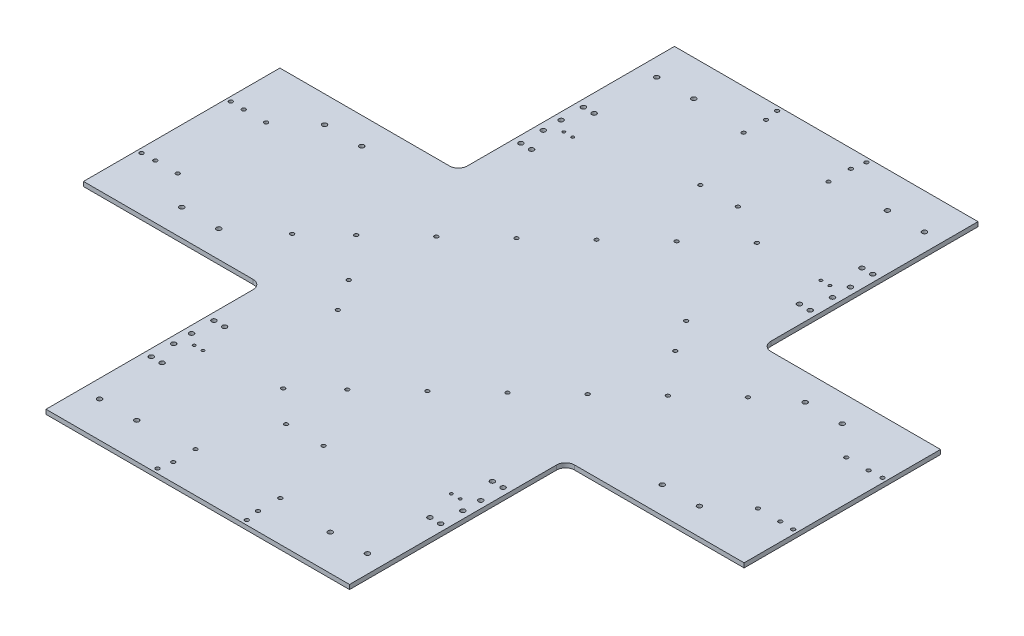
SolidWorks part; units mm, degrees
other "Markup1"
sketch "Sketch8"
material "3.0205 (EN-AW 1200)"
ref_plane "前视基准面" through (0, 0, 0) normal (0, 0, 1) x (1, 0, 0)
ref_plane "上视基准面" through (0, 0, 0) normal (0, 1, 0) x (1, 0, 0)
ref_plane "右视基准面" through (0, 0, 0) normal (1, 0, 0) x (0, 0, -1)
other "Configuration Table"
sketch "Sketch1" plane through (0, 0, 0) normal (0, 1, 0) x (1, 0, 0)
  line L0 (170, 352) -> (-170, 352)
  line L1 (-170, 352) -> (-170, 110)
  line L2 (-170, 110) -> (-370, 110)
  line L5 (-370, 110) -> (-370, -110)
  line L6 (0, 352) -> (0, -66.8675) construction
  line L7 (-370, 0) -> (131.0517, 0) construction
  line L8 (370, 110) -> (370, -110)
  line L11 (170, 110) -> (370, 110)
  line L12 (170, 352) -> (170, 110)
  line L13 (170, -352) -> (170, -110)
  line L14 (170, -110) -> (370, -110)
  line L19 (-170, -110) -> (-370, -110)
  line L20 (-170, -352) -> (-170, -110)
  line L21 (170, -352) -> (-170, -352)
  point P21 (370, 0)
  dimension "D1" = 170
  dimension "D2" = 200
  dimension "D3" = 110
  dimension "D4" = 242
extrude "Boss-Extrude1" add sketch "Sketch1" along normal blind 5
sketch "Sketch2" plane through (0, 5, 0) normal (0, 1, 0) x (1, 0, 0)
  line L3 (370, -110) -> (370, 110) construction
  line L4 (-56.7455, 0) -> (47.5165, 0) construction
  line L5 (0, 54.7142) -> (0, -64.2255) construction
  line L7 (170, 352) -> (-170, 352) construction
  circle A0 centre (350, 49.5) radius 2.125
  circle A1 centre (325, 49.5) radius 2.125
  circle A7 centre (325, -49.5) radius 2.125
  circle A8 centre (350, -49.5) radius 2.125
  circle A9 centre (-350, -49.5) radius 2.125
  circle A10 centre (-325, -49.5) radius 2.125
  circle A13 centre (-325, 49.5) radius 2.125
  circle A14 centre (-350, 49.5) radius 2.125
  circle A15 centre (47.5, 332) radius 2.125
  circle A16 centre (47.5, 307) radius 2.125
  circle A17 centre (-47.5, 307) radius 2.125
  circle A18 centre (-47.5, 332) radius 2.125
  circle A19 centre (-47.5, -332) radius 2.125
  circle A20 centre (-47.5, -307) radius 2.125
  circle A21 centre (47.5, -307) radius 2.125
  circle A22 centre (47.5, -332) radius 2.125
  dimension "D3" = 49.5
  dimension "D5" = 4.25
  dimension "D7" = 4.25
  dimension "D9" = 4.25
  dimension "D10" = 4.25
  dimension "D2" = 47.5
  dimension "D4" = 25
  dimension "D6" = 20
  dimension "20" = 20
  dimension "D13" = 25
extrude "Cut-Extrude1" cut sketch "Sketch2" against normal blind 3
sketch "Sketch4" plane through (0, 5, 0) normal (0, 1, 0) x (1, 0, 0)
  line L0 (-170, 352) -> (-170, 110) construction
  line L1 (170, 352) -> (-170, 352) construction
  line L2 (0, 46.9886) -> (0, -40.2904) construction
  line L3 (-35.103, 0) -> (92.4951, 0) construction
  line L5 (170, -352) -> (170, -110) construction
  circle A0 centre (-162, 172) radius 2.6
  circle A1 centre (-150, 172) radius 2.6
  circle A2 centre (-162, 197) radius 2.6
  circle A3 centre (-162, 217) radius 2.6
  circle A4 centre (-162, 242) radius 2.6
  circle A5 centre (-150, 242) radius 2.6
  circle A6 centre (150, 242) radius 2.6
  circle A7 centre (162, 242) radius 2.6
  circle A8 centre (162, 217) radius 2.6
  circle A9 centre (162, 197) radius 2.6
  circle A10 centre (150, 172) radius 2.6
  circle A11 centre (162, 172) radius 2.6
  circle A12 centre (162, -172) radius 2.6
  circle A13 centre (150, -172) radius 2.6
  circle A14 centre (162, -197) radius 2.6
  circle A15 centre (162, -217) radius 2.6
  circle A16 centre (162, -242) radius 2.6
  circle A17 centre (150, -242) radius 2.6
  circle A18 centre (-150, -242) radius 2.6
  circle A19 centre (-162, -242) radius 2.6
  circle A20 centre (-162, -217) radius 2.6
  circle A21 centre (-162, -197) radius 2.6
  circle A22 centre (-150, -172) radius 2.6
  circle A23 centre (-162, -172) radius 2.6
  circle A24 centre (149, -207) radius 1.6
  circle A25 centre (-149, -207) radius 1.6
  circle A26 centre (149, 207) radius 1.6
  circle A27 centre (-149, 207) radius 1.6
  circle A28 centre (139, -207) radius 1.6
  circle A29 centre (-139, -207) radius 1.6
  circle A30 centre (139, 207) radius 1.6
  circle A31 centre (-139, 207) radius 1.6
  dimension "D3" = 5.2
  dimension "D4" = 5.2
  dimension "D5" = 8
  dimension "D6" = 8
  dimension "D9" = 5.2
  dimension "D10" = 5.2
  dimension "D11" = 5.2
  dimension "D12" = 5.2
  dimension "D19" = 3.2
  dimension "D20" = 21
  dimension "D21" = 10
  dimension "D22" = 3.2
  dimension "D23" = 10
  dimension "D1" = 8
  dimension "D2" = 20
  dimension "D7" = 8
  dimension "D8" = 20
  dimension "D13" = 25
  dimension "D14" = 20
  dimension "D15" = 25
  dimension "D16" = 25
  dimension "D17" = 110
  dimension "D18" = 0
extrude "Cut-Extrude3" cut sketch "Sketch4" against normal blind 10
sketch "Sketch5" plane through (0, 5, 0) normal (0, 1, 0) x (1, 0, 0)
  line L0 (170, 352) -> (-170, 352) construction
  line L5 (-46.9195, 0) -> (66.6223, 0) construction
  line L6 (0, 59.0569) -> (0, -54.4849) construction
  line L10 (-370, 110) -> (-370, -110) construction
  circle A0 centre (-50, 347) radius 2.125
  circle A1 centre (50, 347) radius 2.125
  circle A2 centre (50, -347) radius 2.125
  circle A3 centre (-50, -347) radius 2.125
  circle A4 centre (-365, 50) radius 2.125
  circle A5 centre (-365, -50) radius 2.125
  circle A6 centre (365, -50) radius 2.125
  circle A7 centre (365, 50) radius 2.125
  dimension "D1" = 4.25
  dimension "D2" = 4.25
  dimension "D3" = 50
  dimension "D6" = 4.25
  dimension "D7" = 4.25
  dimension "5" = 5
  dimension "D4" = 50
  dimension "D5" = 50
  dimension "D8" = 50
  dimension "D9" = 5
  dimension "D10" = 5
extrude "Cut-Extrude4" cut sketch "Sketch5" against normal blind 10
fillet "Fillet1" radius 10 4 edges at (-170, 2.5, -110) (-170, 2.5, 110) (170, 2.5, 110) (170, 2.5, -110)
sketch "Sketch6" plane through (0, 5, 0) normal (0, 1, 0) x (1, 0, 0)
  line L0 (170, 352) -> (-170, 352) construction
  line L1 (-170, 352) -> (-170, 120) construction
  line L3 (0, 50.3702) -> (0, -42.7646) construction
  line L4 (-54.8568, 0) -> (91.2004, 0) construction
  line L5 (370, 110) -> (180, 110) construction
  line L6 (370, -110) -> (370, 110) construction
  circle A0 centre (-150, 312) radius 2.6
  circle A1 centre (-108.4, 312) radius 2.6
  circle A4 centre (108.4, 312) radius 2.6
  circle A5 centre (150, 312) radius 2.6
  circle A6 centre (150, -312) radius 2.6
  circle A7 centre (108.4, -312) radius 2.6
  circle A8 centre (-108.4, -312) radius 2.6
  circle A9 centre (-150, -312) radius 2.6
  circle A10 centre (248.4, 80) radius 2.6
  circle A11 centre (290, 80) radius 2.6
  circle A12 centre (290, -80) radius 2.6
  circle A13 centre (248.4, -80) radius 2.6
  circle A14 centre (-248.4, -80) radius 2.6
  circle A15 centre (-290, -80) radius 2.6
  circle A16 centre (-290, 80) radius 2.6
  circle A17 centre (-248.4, 80) radius 2.6
  dimension "D1" = 5.2
  dimension "D2" = 5.2
  dimension "D3" = 5.2
  dimension "D4" = 5.2
  dimension "D5" = 40
  dimension "D8" = 30
  dimension "D6" = 20
  dimension "D7" = 41.6
  dimension "D9" = 80
  dimension "D10" = 41.6
extrude "Cut-Extrude5" cut sketch "Sketch6" against normal blind 10
sketch "Sketch7" plane through (0, 5, 0) normal (0, 1, 0) x (1, 0, 0)
  line L0 (164.5832, 153.9982) -> (-155.4181, -145.4226) construction
  line L1 (170, 304.2329) -> (-272.7048, -110) construction
  line L2 (170, 120) -> (170, 352) construction
  line L3 (-370, -110) -> (-180, -110) construction
  line L4 (272.7048, 110) -> (-170, -304.2329) construction
  line L5 (370, 110) -> (180, 110) construction
  line L6 (-170, -120) -> (-170, -352) construction
  line L7 (-268.9942, -53.3124) -> (-51.1439, -286.1364) construction
  line L8 (84.7791, 253.9237) -> (328.5288, -6.5799) construction
  line L9 (-72.423, 77.401) -> (72.423, -77.401) construction
  line L11 (-380.0049, -355.5654) -> (380.0049, -355.5654) construction
  line L12 (-380.0049, -355.5654) -> (-380.0049, 355.5654) construction
  line L13 (-380.0049, 355.5654) -> (380.0049, 355.5654) construction
  line L14 (380.0049, -355.5654) -> (380.0049, 355.5654) construction
  line L15 (-380.0049, -355.5654) -> (380.0049, 355.5654) construction
  line L16 (-380.0049, 355.5654) -> (380.0049, -355.5654) construction
  circle A4 centre (-72.423, 77.401) radius 2.125
  circle A5 centre (-26.0555, 120.7864) radius 2.125
  circle A6 centre (20.3121, 164.1719) radius 2.125
  circle A7 centre (66.6796, 207.5574) radius 2.125
  circle A8 centre (-118.7906, 34.0155) radius 2.125
  circle A9 centre (-165.1581, -9.37) radius 2.125
  circle A10 centre (-202.2522, -44.0784) radius 2.125
  circle A11 centre (-57.4061, -198.8803) radius 2.125
  circle A12 centre (-20.3121, -164.1719) radius 2.125
  circle A13 centre (26.0555, -120.7864) radius 2.125
  circle A14 centre (211.5257, 52.7555) radius 2.125
  circle A15 centre (165.1581, 9.37) radius 2.125
  circle A16 centre (118.7906, -34.0155) radius 2.125
  circle A17 centre (72.423, -77.401) radius 2.125
  point P53 (0, 0)
  dimension "D6" = 4.25
  dimension "D7" = 4.25
  dimension "D8" = 4.25
  dimension "D9" = 4.25
  dimension "D10" = 4.25
  dimension "D11" = 4.25
  dimension "D12" = 4.25
  dimension "D1" = 106
  dimension "D3" = 20
  dimension "D4" = 20
  dimension "D5" = 0
  dimension "D13" = 63.5
  dimension "D14" = 63.5
  dimension "D15" = 50.8
  dimension "D16" = 63.5
  dimension "D17" = 63.5
  dimension "D18" = 63.5
extrude "Cut-Extrude6" cut sketch "Sketch7" against normal blind 10
sketch "Sketch9" plane through (0, 5, 0) normal (0, 1, 0) x (1, 0, 0)
  line L0 (172.9289, 112.9289) -> (-172.9289, -112.9289) construction
  line L1 (84.4104, 120.4544) -> (152.5807, 16.0648) construction
  line L2 (-145.1056, -27.5116) -> (-91.0695, -110.2573) construction
  line L3 (0, 45.0584) -> (0, -52.9183) construction
  line L4 (-44.6513, 0) -> (48.0404, 0) construction
  line L5 (170, 352) -> (-170, 352) construction
  arc A0 (170, 120) -> (180, 110) centre (180, 120) ccw construction
  arc A1 (-170, -120) -> (-180, -110) centre (-180, -120) ccw construction
  circle A2 centre (-125.8016, -57.0718) radius 2.1
  circle A3 centre (-102.8371, -92.2376) radius 2.1
  circle A4 centre (102.8371, 92.2376) radius 2.1
  circle A5 centre (125.8016, 57.0718) radius 2.1
  circle A7 centre (21, 232) radius 2.1
  circle A8 centre (-21, 232) radius 2.1
  circle A9 centre (-21, -232) radius 2.1
  circle A10 centre (21, -232) radius 2.1
  dimension "D3" = 4.2
  dimension "D4" = 4.2
  dimension "D5" = 4.2
  dimension "D6" = 4.2
  dimension "D11" = 120
  dimension "D12" = 4.2
  dimension "D1" = 70
  dimension "D2" = 70
  dimension "D7" = 21
  dimension "D8" = 21
  dimension "D9" = 21
  dimension "D10" = 21
  dimension "D13" = 21
extrude "Cut-Extrude7" cut sketch "Sketch9" against normal blind 10
